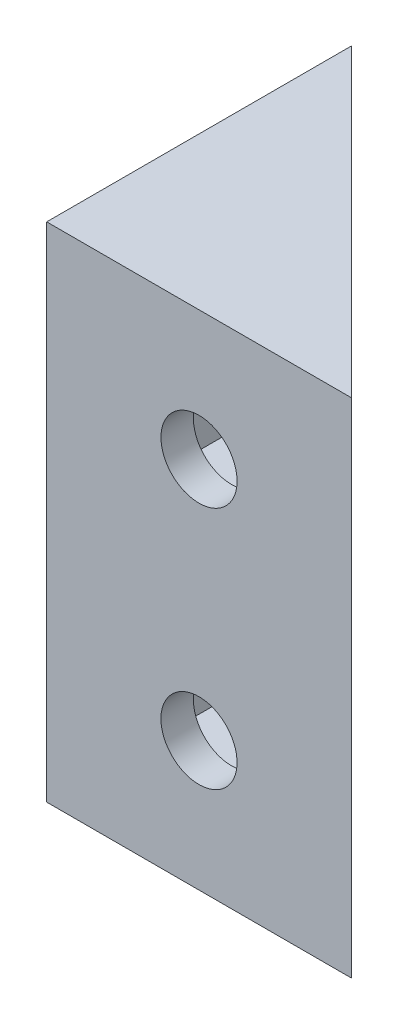
SolidWorks part; units mm, degrees
ref_plane "Спереди" through (0, 0, 0) normal (0, 0, 1) x (1, 0, 0)
ref_plane "Сверху" through (0, 0, 0) normal (0, 1, 0) x (1, 0, 0)
ref_plane "Справа" through (0, 0, 0) normal (1, 0, 0) x (0, 0, -1)
sketch "Эскиз1" plane through (0, 0, 0) normal (0, 1, 0) x (1, 0, 0)
  line L0 (0, 0) -> (0, 20)
  line L1 (0, 0) -> (20, 0)
  line L2 (20, 0) -> (17, 3)
  line L3 (17, 3) -> (3, 3)
  line L4 (3, 3) -> (3, 17)
  line L5 (3, 17) -> (0, 20)
  dimension "D1" = 20
  dimension "D2" = 20
  dimension "D3" = 3
  dimension "D4" = 3
  dimension "D5" = 45
  dimension "D6" = 45
extrude "Бобышка-Вытянуть1" add sketch "Эскиз1" along normal blind 16.5 and the other way blind 16.5
sketch "Эскиз2" plane through (0, 16.5, 0) normal (0, 1, 0) x (1, 0, 0)
  line L0 (0, 20) -> (0, 0)
  line L1 (0, 0) -> (20, 0)
  line L2 (20, 0) -> (0, 20)
extrude "Бобышка-Вытянуть2" add sketch "Эскиз2" against normal blind 3
sketch "Эскиз3" plane through (0, -16.5, 0) normal (0, -1, 0) x (-1, 0, 0)
  line L0 (0, 0) -> (-20, 0)
  line L1 (-20, 0) -> (0, 20)
  line L2 (0, 20) -> (0, 0)
extrude "Бобышка-Вытянуть3" add sketch "Эскиз3" against normal blind 3
sketch "Эскиз4" plane through (0, 0, 0) normal (0, 1, 0) x (1, 0, 0)
  line L0 (20, 0) -> (0, 0)
  line L1 (0, 0) -> (0, 20)
  line L2 (0, 20) -> (20, 0)
extrude "Бобышка-Вытянуть4" add sketch "Эскиз4" along normal blind 1.5 and the other way blind 1.5
sketch "Эскиз5" plane through (0, 0, 0) normal (0, 0, 1) x (1, 0, 0)
  line L0 (0, 0) -> (20, 0) construction
  line L1 (20, -16.5) -> (20, 16.5) construction
  line L2 (10, 0) -> (10, 8) construction
  circle A0 centre (10, 8) radius 2.5
  circle A1 centre (10, -8) radius 2.5
  dimension "D1" = 5
  dimension "D2" = 16
extrude "Вырез-Вытянуть1" cut sketch "Эскиз5" against normal through all
sketch "Эскиз6" plane through (0, 0, 0) normal (-1, 0, 0) x (0, 0, 1)
  line L0 (0, 0) -> (-20, 0) construction
  line L1 (0, -16.5) -> (0, 16.5) construction
  line L2 (-20, -16.5) -> (-20, 16.5) construction
  line L3 (-10, 0) -> (-10, 8) construction
  circle A0 centre (-10, 8) radius 2.5
  circle A1 centre (-10, -8) radius 2.5
  dimension "D1" = 5
  dimension "D2" = 16
extrude "Вырез-Вытянуть2" cut sketch "Эскиз6" against normal through all
chamfer "Фаска1" distance 1.5 angle 30 4 edges at (7.5, 8, -3) (7.5, -8, -3) (3, -8, -12.5) (3, 8, -12.5) first distance on face at (7.5, 8, -3) first distance on face at (7.5, -8, -3) first distance on face at (3, -8, -12.5) first distance on face at (3, 8, -12.5)
